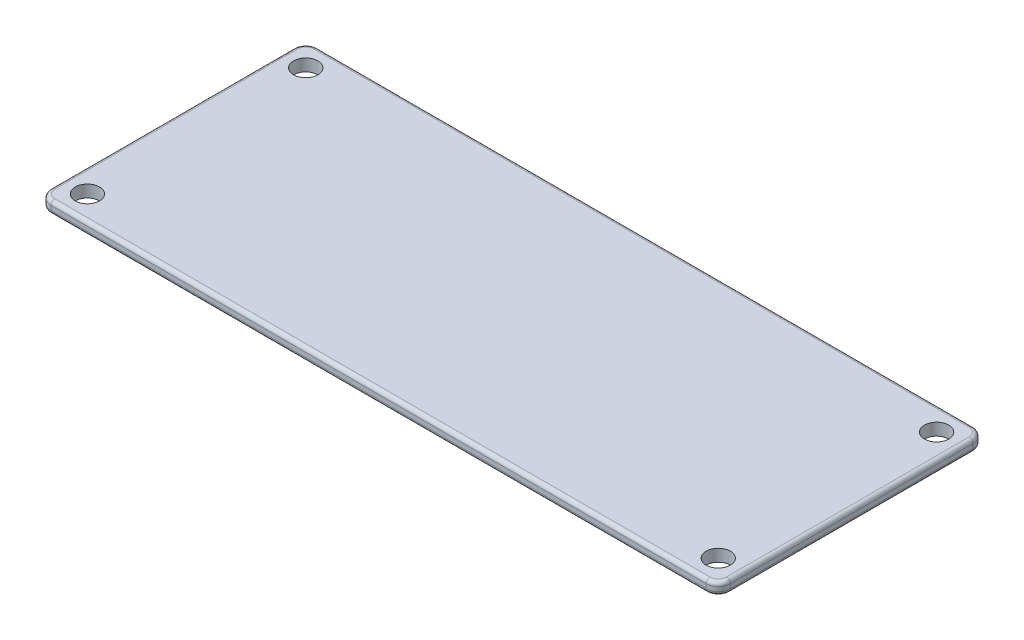
SolidWorks part; units mm, degrees
ref_plane "Front Plane" through (0, 0, 0) normal (0, 0, 1) x (1, 0, 0)
ref_plane "Top Plane" through (0, 0, 0) normal (0, 1, 0) x (1, 0, 0)
ref_plane "Right Plane" through (0, 0, 0) normal (1, 0, 0) x (0, 0, -1)
sketch "Sketch1" plane through (0, 0, 0) normal (0, 1, 0) x (1, 0, 0)
  line L1 (-88.9, -34.925) -> (88.9, -34.925)
  line L2 (-88.9, -34.925) -> (-88.9, 34.925)
  line L3 (-88.9, 34.925) -> (88.9, 34.925)
  line L4 (88.9, -34.925) -> (88.9, 34.925)
  line L5 (-88.9, -34.925) -> (88.9, 34.925) construction
  line L6 (-88.9, 34.925) -> (88.9, -34.925) construction
  point P0 (0, 0)
  dimension "D1" = 69.85
  dimension "D2" = 177.8
extrude "Boss-Extrude1" add sketch "Sketch1" along normal blind 3.175
sketch "Sketch2" plane through (0, 3.175, 0) normal (0, 1, 0) x (1, 0, 0)
  line L0 (-88.9, 34.925) -> (-88.9, -34.925) construction
  line L1 (-82.55, -28.575) -> (82.55, -28.575) construction
  line L2 (-82.55, -28.575) -> (-82.55, 28.575) construction
  line L3 (-82.55, 28.575) -> (82.55, 28.575) construction
  line L4 (82.55, -28.575) -> (82.55, 28.575) construction
  line L5 (-82.55, -28.575) -> (82.55, 28.575) construction
  line L6 (-82.55, 28.575) -> (82.55, -28.575) construction
  line L7 (88.9, 34.925) -> (-88.9, 34.925) construction
  circle A0 centre (-82.55, 28.575) radius 3.175
  circle A1 centre (-82.55, -28.575) radius 3.175
  circle A2 centre (82.55, 28.575) radius 3.175
  circle A3 centre (82.55, -28.575) radius 3.175
  point P0 (0, 0)
  dimension "D1" = 6.35
  dimension "D2" = 6.35
  dimension "D3" = 6.35
  dimension "D4" = 6.35
  dimension "D5" = 6.35
  dimension "D6" = 6.35
extrude "Cut-Extrude1" cut sketch "Sketch2" against normal through all
fillet "Fillet1" radius 3.175 4 edges at (88.9, 1.5875, -34.925) (88.9, 1.5875, 34.925) (-88.9, 1.5875, -34.925) (-88.9, 1.5875, 34.925)
fillet "Fillet2" radius 1 16 edges at (-87.9701, 0, 33.9951) (-88.9, 0, 0) (-87.9701, 0, -33.9951) (0, 0, -34.925) (87.9701, 0, -33.9951) (88.9, 0, 0) (87.9701, 0, 33.9951) (-87.9701, 3.175, 33.9951) (-88.9, 3.175, 0) (-87.9701, 3.175, -33.9951) (0, 3.175, -34.925) (87.9701, 3.175, -33.9951) (88.9, 3.175, 0) (87.9701, 3.175, 33.9951) (0, 0, 34.925) (0, 3.175, 34.925)
